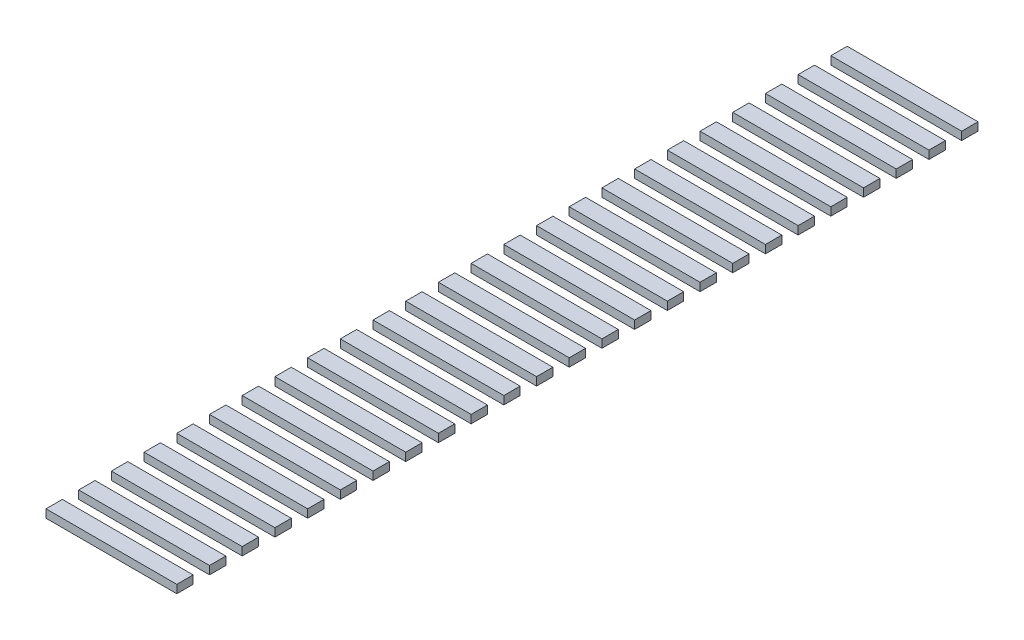
SolidWorks part; units mm, degrees
ref_plane "Front Plane" through (0, 0, 0) normal (0, 0, 1) x (1, 0, 0)
ref_plane "Top Plane" through (0, 0, 0) normal (0, 1, 0) x (1, 0, 0)
ref_plane "Right Plane" through (0, 0, 0) normal (1, 0, 0) x (0, 0, -1)
sketch "Sketch1" plane through (0, 0, 0) normal (0, 1, 0) x (1, 0, 0)
  line L1 (-80, 500) -> (80, 500)
  line L2 (-80, 500) -> (-80, -500)
  line L3 (-80, -500) -> (80, -500)
  line L4 (80, 500) -> (80, -500)
  line L5 (-80, 500) -> (80, -500) construction
  line L6 (-80, -500) -> (80, 500) construction
  point P0 (0, 0)
  dimension "D1" = 160
  dimension "D2" = 1000
extrude "Boss-Extrude1" add sketch "Sketch1" along normal blind 10
sketch "Sketch2" plane through (0, 10, 0) normal (0, 1, 0) x (1, 0, 0)
  line L0 (-80, 500) -> (-80, -500) construction
  line L1 (-80, 480) -> (80, 480)
  line L2 (-80, 480) -> (-80, 460)
  line L3 (-80, 460) -> (80, 460)
  line L4 (80, 480) -> (80, 460)
  line L5 (80, -500) -> (80, 500) construction
  line L6 (80, 500) -> (-80, 500) construction
  dimension "D1" = 20
  dimension "D2" = 20
extrude "Cut-Extrude1" cut sketch "Sketch2" against normal up to next
pattern_linear "LPattern1" count 25 spacing 40 along (0, 0, 1) of "Cut-Extrude1"
